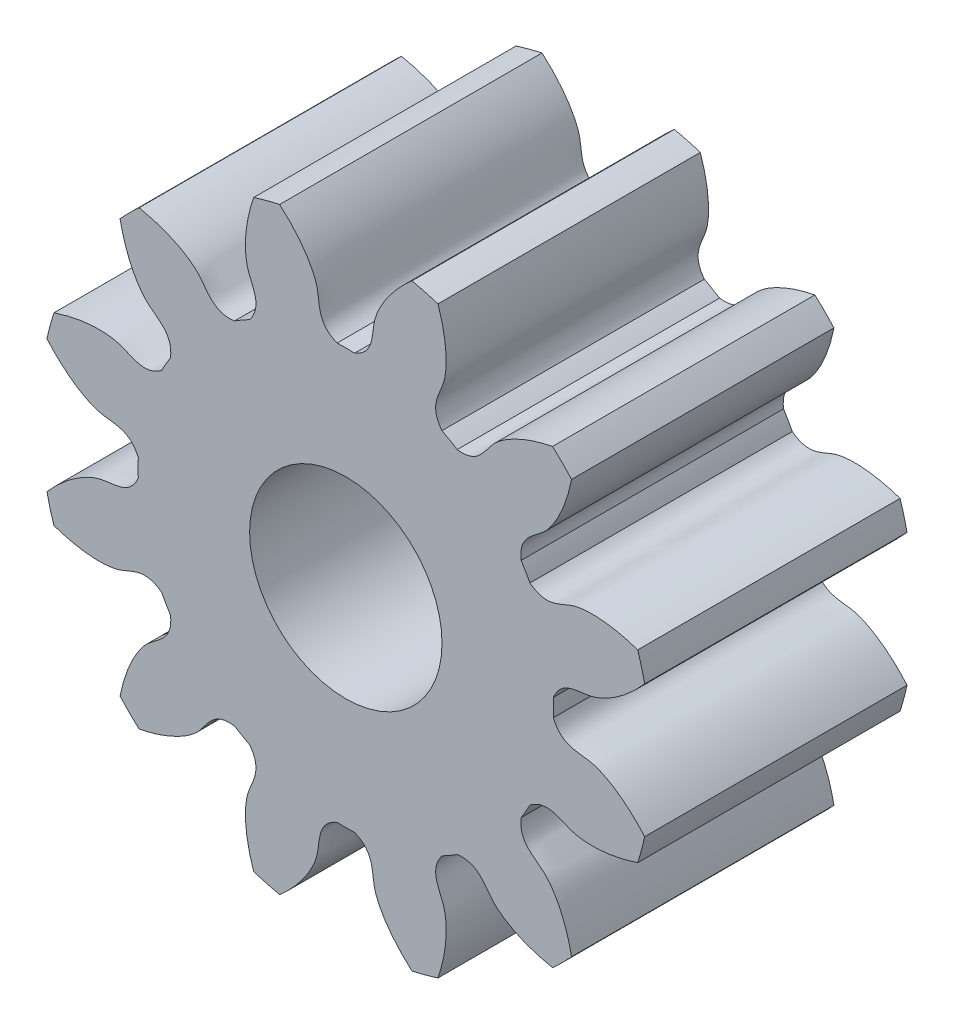
SolidWorks part; units mm, degrees
ref_plane "前视基准面" through (0, 0, 0) normal (0, 0, 1) x (1, 0, 0)
ref_plane "上视基准面" through (0, 0, 0) normal (0, 1, 0) x (1, 0, 0)
ref_plane "右视基准面" through (0, 0, 0) normal (1, 0, 0) x (0, 0, -1)
other "Configuration Table"
sketch "草图1" plane through (0, 0, 0) normal (0, 0, 1) x (1, 0, 0)
  circle A0 centre (0, 0) radius 3.5
extrude "凸台-拉伸1" add sketch "草图1" along normal blind 3
ref_axis "基准轴1" through (0, 0, 3) along (0, 0, -1)
sketch "草图2" plane through (0, 0, 0) normal (0, 0, 1) x (1, 0, 0)
  line L0 (0, 0) -> (0, 3.5) construction
  circle A0 centre (0, 0) radius 3.5 construction
  arc A1 (0.1004, 2.3729) -> (-0.1004, 2.3729) centre (0, 0) ccw
  arc A2 (1.7488, 3.9475) -> (-1.7488, 3.9475) centre (0, 0) ccw
  spline S0 degree 3 poles (0.1004, 2.3729) (0.3404, 2.4747) (0.2872, 2.6724) (0.3381, 2.8447) (0.3413, 2.855) (0.3451, 2.8662) (0.3495, 2.8784) (0.3546, 2.8915) (0.3603, 2.9056) (0.3668, 2.9206) (0.374, 2.9366) (0.3821, 2.9533) (0.3909, 2.971) (0.4007, 2.9894) (0.4114, 3.0086) (0.423, 3.0286) (0.4356, 3.0493) (0.4492, 3.0707) (0.4639, 3.0928) (0.4796, 3.1155) (0.4965, 3.1388) (0.5145, 3.1626) (0.5337, 3.187) (0.554, 3.2119) (0.5756, 3.2372) (0.5985, 3.2629) (0.6226, 3.289) (0.648, 3.3154) (0.6748, 3.342) (0.7028, 3.369) (0.7323, 3.3961) (0.7631, 3.4234) (0.7954, 3.4507) (0.829, 3.4782) (0.8641, 3.5057) (0.9006, 3.5331) (0.9385, 3.5604) (0.978, 3.5877) (1.0189, 3.6147) (1.0613, 3.6416) (1.1052, 3.6681) (1.1506, 3.6944) (1.1975, 3.7203) (1.2459, 3.7457) (1.2958, 3.7707) (1.3472, 3.7952) (1.4001, 3.8191) (1.4546, 3.8424) (1.5105, 3.865) (1.5679, 3.8869) (1.6472, 3.9154) (1.7078, 3.9351) (1.7488, 3.9475) knots 0 0 0 0 0.218015 0.222044 0.226546 0.231522 0.236972 0.242897 0.249295 0.256167 0.263513 0.271332 0.279626 0.288394 0.297636 0.307351 0.317541 0.328204 0.339341 0.350953 0.363038 0.375597 0.38863 0.402137 0.416118 0.430573 0.445502 0.460904 0.476781 0.493132 0.509956 0.527255 0.545027 0.563273 0.581994 0.601188 0.620856 0.640998 0.661614 0.682704 0.704268 0.726305 0.748817 0.771803 0.795262 0.819196 0.843603 0.868484 0.89384 0.919669 0.945972 1 1 1 1
  spline S1 degree 3 poles (-0.1004, 2.3729) (-0.3404, 2.4747) (-0.2872, 2.6724) (-0.3381, 2.8447) (-0.3413, 2.855) (-0.3451, 2.8662) (-0.3495, 2.8784) (-0.3546, 2.8915) (-0.3603, 2.9056) (-0.3668, 2.9206) (-0.374, 2.9366) (-0.3821, 2.9533) (-0.3909, 2.971) (-0.4007, 2.9894) (-0.4114, 3.0086) (-0.423, 3.0286) (-0.4356, 3.0493) (-0.4492, 3.0707) (-0.4639, 3.0928) (-0.4796, 3.1155) (-0.4965, 3.1388) (-0.5145, 3.1626) (-0.5337, 3.187) (-0.554, 3.2119) (-0.5756, 3.2372) (-0.5985, 3.2629) (-0.6226, 3.289) (-0.648, 3.3154) (-0.6748, 3.342) (-0.7028, 3.369) (-0.7323, 3.3961) (-0.7631, 3.4234) (-0.7954, 3.4507) (-0.829, 3.4782) (-0.8641, 3.5057) (-0.9006, 3.5331) (-0.9385, 3.5604) (-0.978, 3.5877) (-1.0189, 3.6147) (-1.0613, 3.6416) (-1.1052, 3.6681) (-1.1506, 3.6944) (-1.1975, 3.7203) (-1.2459, 3.7457) (-1.2958, 3.7707) (-1.3472, 3.7952) (-1.4001, 3.8191) (-1.4546, 3.8424) (-1.5105, 3.865) (-1.5679, 3.8869) (-1.6472, 3.9154) (-1.7078, 3.9351) (-1.7488, 3.9475) knots 0 0 0 0 0.218015 0.222044 0.226546 0.231522 0.236972 0.242897 0.249295 0.256167 0.263513 0.271332 0.279626 0.288394 0.297636 0.307351 0.317541 0.328204 0.339341 0.350953 0.363038 0.375597 0.38863 0.402137 0.416118 0.430573 0.445502 0.460904 0.476781 0.493132 0.509956 0.527255 0.545027 0.563273 0.581994 0.601188 0.620856 0.640998 0.661614 0.682704 0.704268 0.726305 0.748817 0.771803 0.795262 0.819196 0.843603 0.868484 0.89384 0.919669 0.945972 1 1 1 1
extrude "切除-拉伸1" cut sketch "草图2" along normal through all
pattern_circular "阵列(圆周)1" count 12 over 360 about axis through (0, 0, 3) along (0, 0, -1) of "切除-拉伸1"
sketch "草图3" plane through (0, 0, 0) normal (0, 0, 1) x (1, 0, 0)
  circle A0 centre (0, 0) radius 3 construction
  dimension "Dn" = 6
sketch "草图5" plane through (0, 0, 3) normal (0, 0, 1) x (1, 0, 0)
  circle A0 centre (0, 0) radius 1.1
  dimension "D1" = 2.2
extrude "切除-拉伸2" cut sketch "草图5" against normal up to next
